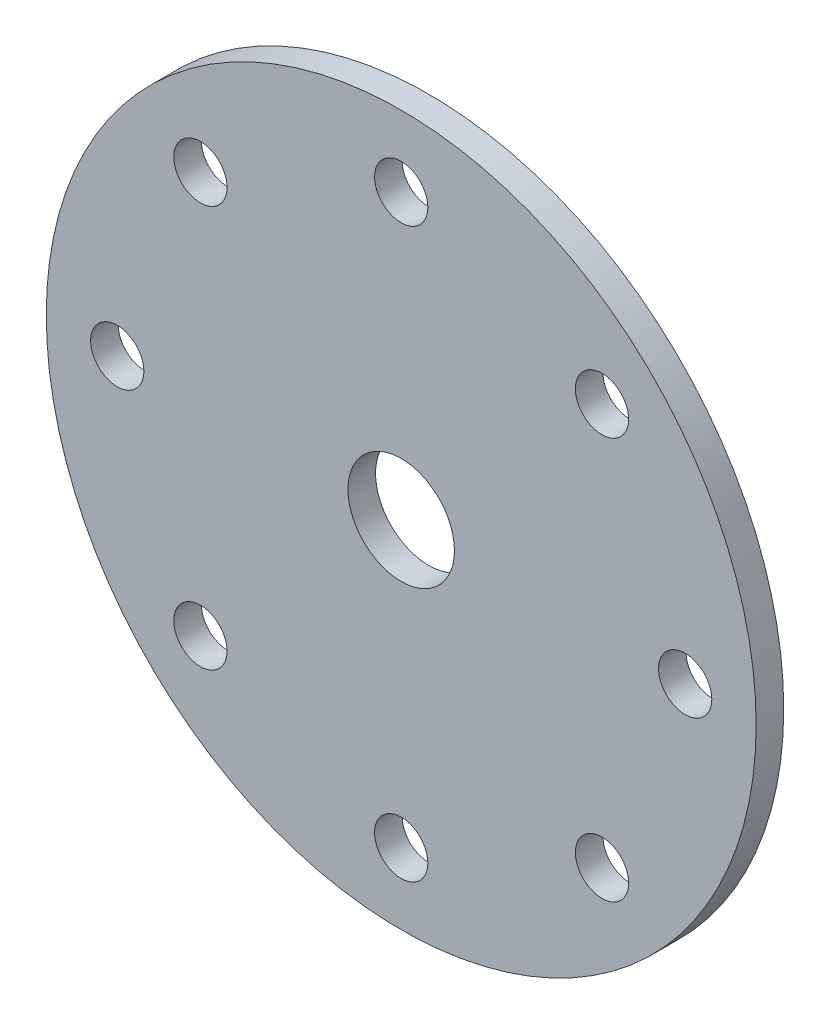
SolidWorks part; units mm, degrees
material "Plain Carbon Steel"
ref_plane "Front Plane" through (0, 0, 0) normal (0, 0, 1) x (1, 0, 0)
ref_plane "Top Plane" through (0, 0, 0) normal (0, 1, 0) x (1, 0, 0)
ref_plane "Right Plane" through (0, 0, 0) normal (1, 0, 0) x (0, 0, -1)
sketch "Sketch1" plane through (0, 0, 0) normal (0, 0, 1) x (1, 0, 0)
  line L0 (0, 63.5) -> (0, -63.5) construction
  line L1 (-63.5, 0) -> (63.5, 0) construction
  line L2 (-35.921, 35.921) -> (35.921, -35.921) construction
  line L3 (-35.921, -35.921) -> (35.921, 35.921) construction
  circle A0 centre (0, 0) radius 63.5
  circle A1 centre (0, 0) radius 9.525
  circle A2 centre (0, 50.8) radius 4.7625
  circle A6 centre (35.921, 35.921) radius 4.7625
  circle A7 centre (50.8, 0) radius 4.7625
  circle A8 centre (35.921, -35.921) radius 4.7625
  circle A9 centre (0, -50.8) radius 4.7625
  circle A10 centre (-35.921, -35.921) radius 4.7625
  circle A11 centre (-50.8, 0) radius 4.7625
  circle A12 centre (-35.921, 35.921) radius 4.7625
  dimension "D1" = 127
  dimension "D2" = 19.05
  dimension "D3" = 9.525
  dimension "D6" = 12.7
  dimension "D4" = 12.7
  dimension "D5" = 8
extrude "Rotor Disc" add sketch "Sketch1" along normal blind 4.9352 contours A0 A12 A11 A10 A8 A7 A6 A1 A2 region at (-61.7039, 0, 0)
